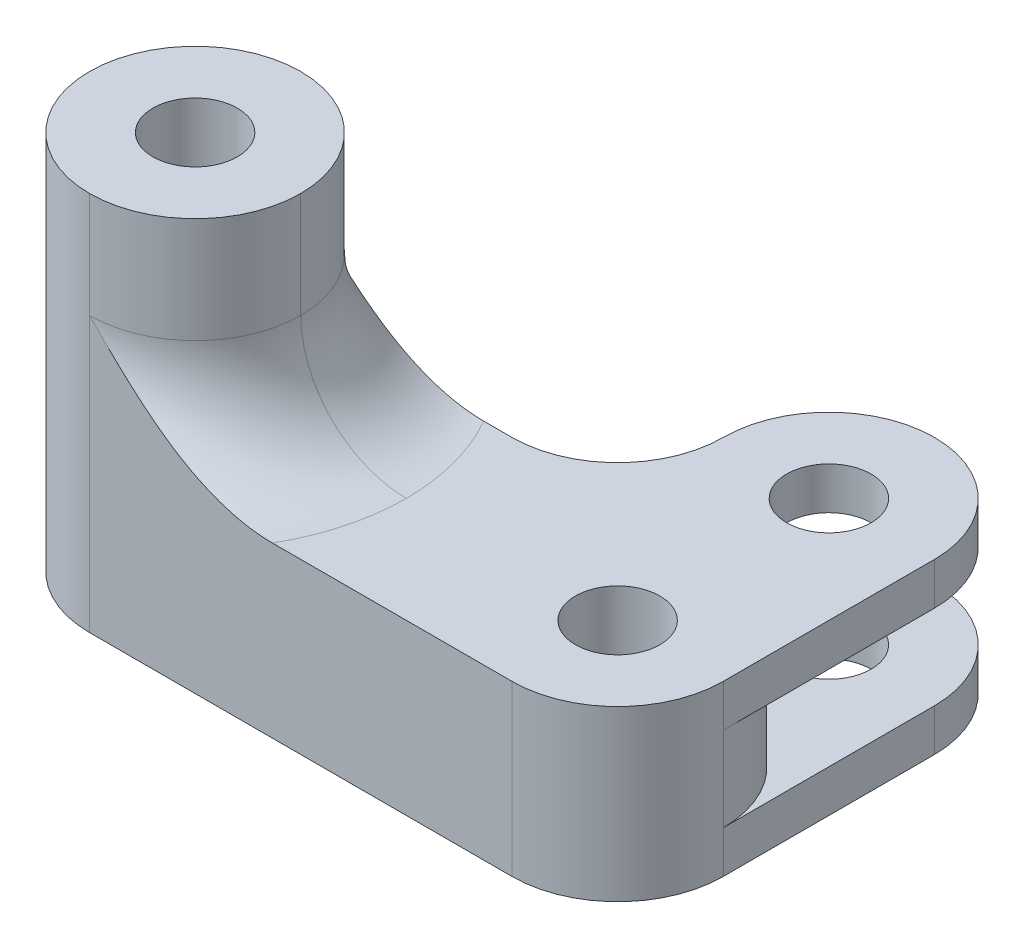
SolidWorks part; units mm, degrees
material "Balsa"
ref_plane "Alzado" through (0, 0, 0) normal (0, 0, 1) x (1, 0, 0)
ref_plane "Planta" through (0, 0, 0) normal (0, 1, 0) x (1, 0, 0)
ref_plane "Vista lateral" through (0, 0, 0) normal (1, 0, 0) x (0, 0, -1)
sketch "Croquis1" plane through (0, 0, 0) normal (0, 1, 0) x (1, 0, 0)
  line L6 (0, 0) -> (0, 10)
  line L7 (0, 10) -> (5, 10)
  line L8 (5, 10) -> (5, 5)
  line L9 (5, 5) -> (15, 5)
  line L10 (15, 5) -> (15, 0)
  line L11 (15, 0) -> (0, 0)
  dimension "D1" = 5
  dimension "D2" = 10
  dimension "D3" = 15
  dimension "D4" = 5
extrude "Saliente-Extruir1" add sketch "Croquis1" along normal blind 4
sketch "Croquis2" plane through (0, 4, 0) normal (0, 1, 0) x (1, 0, 0)
  line L0 (0, 10) -> (5, 5) construction
  line L1 (5, 5) -> (0, 0) construction
  line L3 (5, 10) -> (0, 5) construction
  line L4 (0, 10) -> (0, 0) construction
  line L5 (0, 5) -> (5, 0) construction
  line L6 (0, 0) -> (15, 0) construction
  line L8 (15, 5) -> (10, 0) construction
  line L9 (15, 0) -> (10, 5) construction
  line L12 (15, 5) -> (5, 5) construction
  circle A4 centre (2.5, 7.5) radius 1
  circle A5 centre (2.5, 2.5) radius 1
  circle A6 centre (12.5, 2.5) radius 1
  dimension "D1" = 45
  dimension "D2" = 2
  dimension "D3" = 2
  dimension "D4" = 2
extrude "Cortar-Extruir1" cut sketch "Croquis2" against normal through all
sketch "Croquis3" plane through (0, 4, 0) normal (0, 1, 0) x (1, 0, 0)
  line L1 (10, 5) -> (15, 5)
  line L2 (10, 5) -> (10, 0)
  line L3 (10, 0) -> (15, 0)
  line L4 (15, 5) -> (15, 0)
  line L5 (10, 5) -> (15, 0) construction
  line L6 (10, 0) -> (15, 5) construction
  circle A0 centre (12.5, 2.5) radius 1 construction
  circle A1 centre (12.5, 2.5) radius 1
  point P0 (12.5, 2.5)
extrude "Saliente-Extruir2" add sketch "Croquis3" along normal blind 5
sketch "Croquis4" plane through (0, 0, -10) normal (0, 0, -1) x (-1, 0, 0)
  line L0 (0, 2) -> (-5, 2) construction
  line L1 (0, 4) -> (0, 0) construction
  line L2 (-5, 4) -> (-5, 0) construction
  line L3 (-5, 4) -> (-5, 0) construction
  line L4 (0, 3) -> (-5, 3)
  line L5 (0, 3) -> (0, 1)
  line L6 (0, 1) -> (-5, 1)
  line L7 (-5, 3) -> (-5, 1)
  line L8 (0, 3) -> (-5, 1) construction
  line L9 (0, 1) -> (-5, 3) construction
  point P6 (-2.5, 2)
  dimension "D1" = 2
extrude "Cortar-Extruir2" cut sketch "Croquis4" against normal blind 5
fillet "Redondeo1" radius 2.5 12 edges at (0, 2, -5) (15, 4.5, 0) (0, 2, 0) (0, 3.5, -10) (0, 0.5, -10) (5, 0.5, -10) (5, 0.5, -5) (5, 3.5, -5) (5, 3.5, -10) (10, 6.5, -5) (15, 4.5, -5) (10, 6.5, 0)
fillet "Redondeo2" radius 2.5 2 edges at (10.7322, 4, -0.7322) (10.7322, 4, -4.2678)
ref_plane "Plano1" through (-10, 0, 0) normal (-1, 0, 0) x (0, 0, 1)
mirror "Simetría1" about plane through (-10, 0, 0) normal (-1, 0, 0) of bodies 109
sketch "Croquis5" plane through (0, 0, 0) normal (0, 0, 1) x (1, 0, 0)
  line L1 (18.8533, 10.5025) -> (-5.0194, 10.5025)
  line L2 (18.8533, 10.5025) -> (18.8533, -6.5004)
  line L3 (18.8533, -6.5004) -> (-5.0194, -6.5004)
  line L4 (-5.0194, 10.5025) -> (-5.0194, -6.5004)
  line L5 (18.8533, 10.5025) -> (-5.0194, -6.5004) construction
  line L6 (18.8533, -6.5004) -> (-5.0194, 10.5025) construction
  point P0 (6.917, 2.0011)
extrude "Cortar-Extruir3" cut sketch "Croquis5" against normal blind 10
